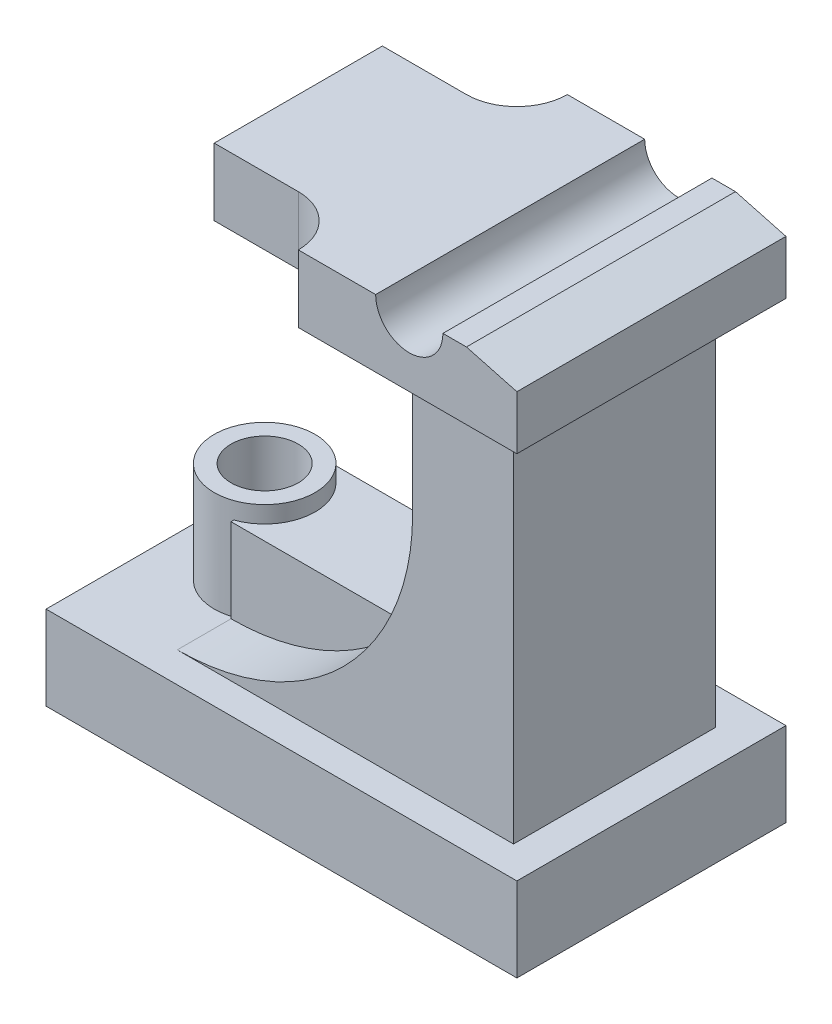
SolidWorks part; units mm, degrees
ref_plane "Front Plane" through (0, 0, 0) normal (0, 0, 1) x (1, 0, 0)
ref_plane "Top Plane" through (0, 0, 0) normal (0, 1, 0) x (1, 0, 0)
ref_plane "Right Plane" through (0, 0, 0) normal (1, 0, 0) x (0, 0, -1)
sketch "Sketch1" plane through (0, 0, 0) normal (0, 1, 0) x (1, 0, 0)
  line L1 (-70, 40) -> (70, 40)
  line L2 (-70, 40) -> (-70, -40)
  line L3 (-70, -40) -> (70, -40)
  line L4 (70, 40) -> (70, -40)
  line L5 (-70, 40) -> (70, -40) construction
  line L6 (-70, -40) -> (70, 40) construction
  point P0 (0, 0)
  dimension "D1" = 140
  dimension "D2" = 80
extrude "Boss-Extrude1" add sketch "Sketch1" along normal blind 25
sketch "Sketch2" plane through (0, 25, 0) normal (0, 1, 0) x (1, 0, 0)
  line L0 (30, 28.9995) -> (60, 28.9995)
  line L1 (60, 28.9995) -> (60, -31.0005)
  line L2 (60, -31.0005) -> (30, -31.0005)
  line L3 (30, -31.0005) -> (30, 28.9995)
  line L4 (-70, -40) -> (70, -40) construction
  line L5 (70, -40) -> (70, 40) construction
  dimension "D1" = 60
  dimension "D2" = 30
  dimension "D3" = 8.9995
  dimension "D4" = 10
extrude "Boss-Extrude2" add sketch "Sketch2" along normal blind 110 contours L3 L0 L1 L2
fillet "Fillet1" radius 70 1 edges at (30, 25, 1.0005)
sketch "Sketch4" plane through (0, 25, 0) normal (0, 1, 0) x (1, 0, 0)
  line L0 (-70, 0) -> (-45, 0)
  line L1 (-70, 40) -> (-70, -40) construction
  circle A0 centre (-45, 0) radius 15
  circle A1 centre (-45, 0) radius 10
  line M1 (-40, -31.0005) -> (-40, 28.9995)
  dimension "D1" = 30
  dimension "D2" = 20
  dimension "D3" = 25
extrude "Boss-Extrude4" add sketch "Sketch4" along normal blind 30 contours A1 A0 L0 M1 | A1 A0 M1 | A1 L0 A0 M1 region at (-50.8605, 25, -8.9095) region at (-50.8605, 25, 8.9095) region at (-34.9707, 25, 0)
sketch "Sketch6" plane through (0, 135, 0) normal (0, 1, 0) x (1, 0, 0)
  line L0 (70, 40) -> (70, -40)
  line L1 (70, -40) -> (-35, -40)
  line L2 (-70, -40) -> (70, -40) construction
  line L3 (-35, -40) -> (-35, 40)
  line L4 (70, 40) -> (-70, 40) construction
  line L5 (-35, 40) -> (70, 40)
  dimension "D1" = 105
extrude "Boss-Extrude5" add sketch "Sketch6" along normal blind 20 contours L5 L0 L1 L3
sketch "Sketch7" plane through (0, 0, 40) normal (0, 0, 1) x (1, 0, 0)
  line L0 (-35, 155) -> (38, 155)
  line L1 (70, 155) -> (-35, 155) construction
  circle A0 centre (38, 155) radius 10
  line M4 (70, 155) -> (-35, 155)
  dimension "D2" = 20
  dimension "D1" = 73
extrude "Cut-Extrude1" cut sketch "Sketch7" against normal through all contours A0 M4 | A0 M4 region at (38, 159.2441, 40) region at (38, 150.7559, 40)
chamfer "Chamfer1" distance 15 angle 15 1 edges at (70, 155, 0) first distance on face at (59, 155, 0)
sketch "Sketch13" plane through (0, 25, 0) normal (0, 1, 0) x (1, 0, 0)
  line L1 (-45, -15) -> (16, -15)
  line L2 (-45, 15) -> (16, 15)
  line L5 (16, 15) -> (16, -15)
  circle A0 centre (-45, 0) radius 15
  line M2 (-40, -31.0005) -> (-40, -14.1421)
  line M4 (-40, 14.1421) -> (-40, 28.9995)
extrude "Boss-Extrude8" add sketch "Sketch13" along normal blind 25 contours A0 L1 L5 L2 M2 M4 region at (-8.661, 25, 0)
sketch "Sketch14" plane through (0, 155, 0) normal (0, 1, 0) x (1, 0, 0)
  line L0 (0, 0) -> (-70, 0) construction
  line L1 (-35, 40) -> (5, 40)
  line L2 (-35, 40) -> (-35, 25)
  line L3 (-35, 25) -> (5, 25)
  line L4 (5, 40) -> (5, 25)
  line L5 (-70, 40) -> (-70, -40) construction
  line L6 (-35, -25) -> (5, -25)
  line L7 (5, -40) -> (5, -25)
  line L8 (-35, -40) -> (5, -40)
  line L9 (-35, -40) -> (-35, -25)
  dimension "D1" = 40
  dimension "D2" = 15
extrude "Cut-Extrude4" cut sketch "Sketch14" against normal blind 20 contours L2 L1 L4 L3 | L6 L7 L8 L9
fillet "Fillet2" radius 15 2 edges at (5, 145, -25) (5, 145, 25)
